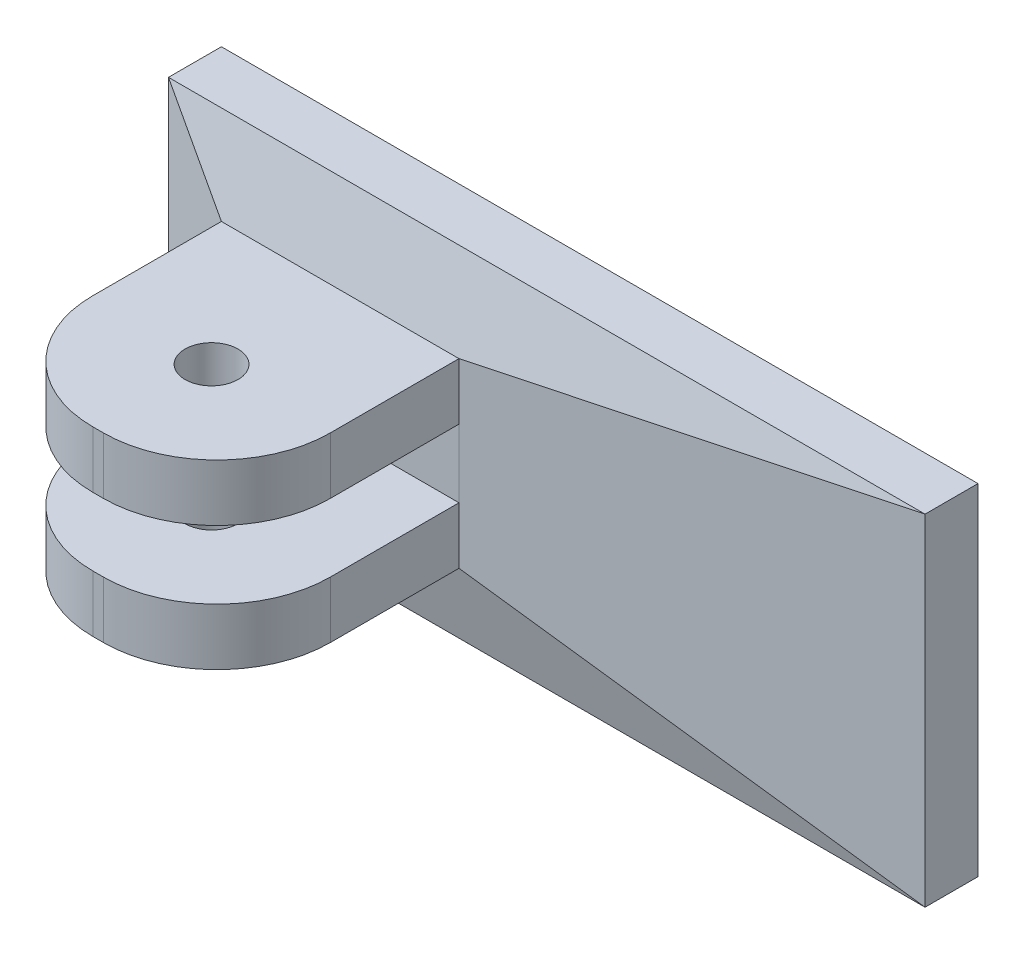
SolidWorks part; units mm, degrees
ref_plane "Front Plane" through (0, 0, 0) normal (0, 0, 1) x (1, 0, 0)
ref_plane "Top Plane" through (0, 0, 0) normal (0, 1, 0) x (1, 0, 0)
ref_plane "Right Plane" through (0, 0, 0) normal (1, 0, 0) x (0, 0, -1)
sketch "Sketch1" plane through (0, 0, 0) normal (0, 0, 1) x (1, 0, 0)
  line L0 (-36.8379, 0) -> (35.7924, 0) construction
  line L1 (-9.658, 0) -> (9.6311, 0) construction
  line L2 (0, 28.0357) -> (0, -21.5283) construction
  line L16 (-23.95, 14.8522) -> (76.05, 14.8522)
  line L17 (-23.95, 14.8522) -> (-23.95, -30.1478)
  line L18 (-23.95, -30.1478) -> (76.05, -30.1478)
  line L19 (76.05, 14.8522) -> (76.05, -30.1478)
  dimension "D1" = 100
  dimension "D2" = 45
extrude "Boss-Extrude1" add sketch "Sketch1" along normal blind 10
sketch "Sketch3" plane through (0, 0, 10) normal (0, 0, 1) x (1, 0, 0)
  line L0 (76.05, 14.8522) -> (-23.95, 14.8522) construction
  line L1 (-13.95, 4.8522) -> (17.45, 4.8522)
  line L2 (-13.95, 4.8522) -> (-13.95, -2.6478)
  line L3 (-13.95, -2.6478) -> (17.45, -2.6478)
  line L4 (17.45, 4.8522) -> (17.45, -2.6478)
  line L5 (-23.95, 14.8522) -> (-23.95, -30.1478) construction
  dimension "D1" = 31.4
  dimension "D2" = 7.5
  dimension "D3" = 10
  dimension "D4" = 10
extrude "Boss-Extrude2" add sketch "Sketch3" along normal blind 5
sketch "Sketch4" plane through (0, -2.6478, 0) normal (0, -1, 0) x (1, 0, 0)
  line L0 (-13.95, 15) -> (-13.95, 27)
  line L1 (1.05, 42) -> (2.45, 42)
  line L2 (17.45, 27) -> (17.45, 15)
  line L3 (-13.95, 15) -> (17.45, 15)
  arc A0 (-13.95, 27) -> (1.05, 42) centre (1.05, 27) cw
  arc A1 (2.45, 42) -> (17.45, 27) centre (2.45, 27) cw
  circle A2 centre (1.7449, 27) radius 3.5
  point P11 (17.45, 42)
  dimension "D2" = 15
  dimension "D3" = 15
  dimension "D1" = 27
extrude "Boss-Extrude3" add sketch "Sketch4" against normal blind 7.5
ref_plane "Plane1" through (0, -7.1478, 0) normal (0, -1, 0) x (-1, 0, 0)
mirror "Mirror1" about plane through (0, -7.1478, 0) normal (0, -1, 0) of "Boss-Extrude3", "Boss-Extrude2"
sketch "Sketch5" plane through (0, -30.1478, 0) normal (0, -1, 0) x (1, 0, 0)
  line L0 (-13.95, 10) -> (-23.95, 7)
  line L1 (-23.95, 10) -> (-23.95, 0) construction
  line L2 (-23.95, 7) -> (-23.95, 10)
  line L3 (-23.95, 10) -> (-13.95, 10)
  line L4 (17.45, 10) -> (76.05, 7)
  line L5 (76.05, 10) -> (76.05, 0) construction
  line L6 (76.05, 7) -> (76.05, 10)
  line L7 (76.05, 10) -> (17.45, 10)
  dimension "D1" = 3
  dimension "D2" = 3
extrude "Cut-Extrude1" cut sketch "Sketch5" against normal blind 45
sketch "Sketch6" plane through (-23.95, 0, 0) normal (-1, 0, 0) x (0, 0, 1)
  line L0 (7, 14.8522) -> (10, 4.8522)
  line L1 (10, 4.8522) -> (10, 14.8522)
  line L2 (10, 14.8522) -> (7, 14.8522)
  line L3 (10, -19.1478) -> (7, -30.1478)
  line L4 (7, -30.1478) -> (10, -30.1478)
  line L5 (10, -30.1478) -> (10, -19.1478)
extrude "Cut-Extrude2" cut sketch "Sketch6" against normal blind 100
